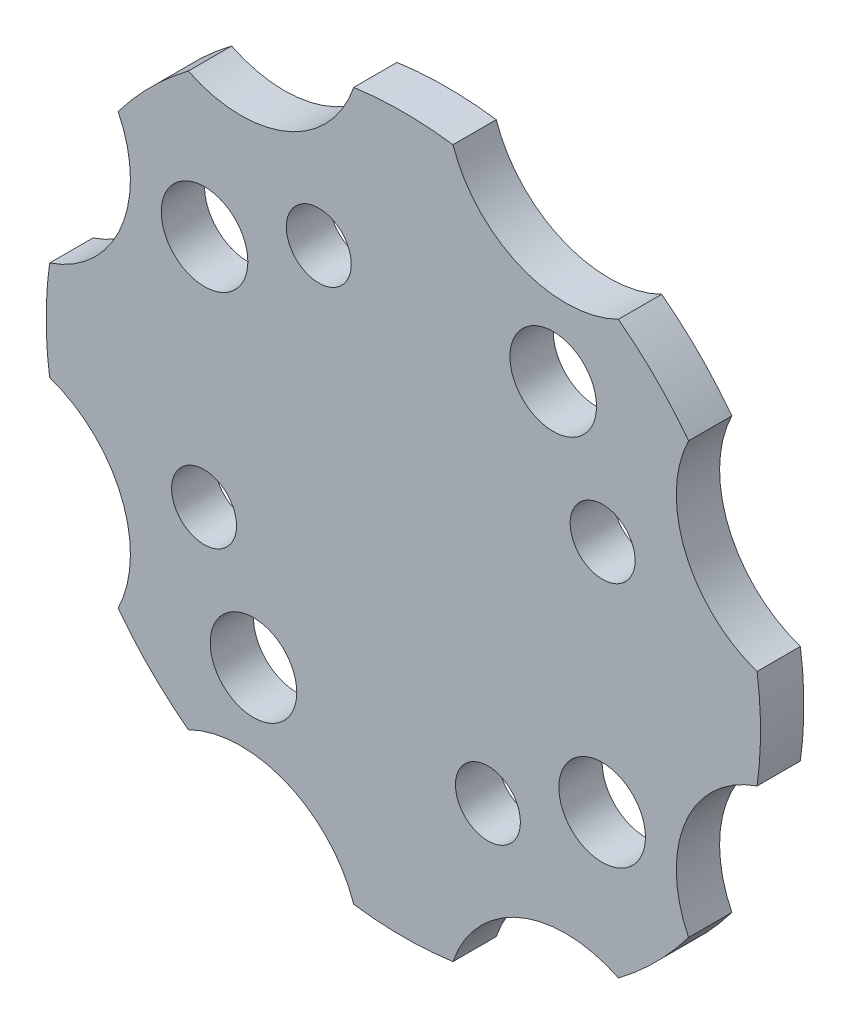
SolidWorks part; units mm, degrees
ref_plane "Front Plane" through (0, 0, 0) normal (0, 0, 1) x (1, 0, 0)
ref_plane "Top Plane" through (0, 0, 0) normal (0, 1, 0) x (1, 0, 0)
ref_plane "Right Plane" through (0, 0, 0) normal (1, 0, 0) x (0, 0, -1)
sketch "Sketch1" plane through (0, 0, 0) normal (0, 0, 1) x (1, 0, 0)
  line L0 (0, 40.4) -> (0, 0)
  line L1 (0, 0) -> (-28.5671, 28.5671)
  line L2 (-27.1179, 29.9463) -> (-11.3901, 14.2185)
  line L3 (-2, 40.3505) -> (-2, 18.108)
  line L4 (2, 40.3505) -> (2, 18.108)
  line L5 (27.1179, 29.9463) -> (11.3901, 14.2185)
  line L6 (29.9463, 27.1179) -> (14.2185, 11.3901)
  line L7 (40.3505, 2) -> (18.108, 2)
  line L8 (40.3505, -2) -> (18.108, -2)
  line L9 (29.9463, -27.1179) -> (14.2185, -11.3901)
  line L10 (27.1179, -29.9463) -> (11.3901, -14.2185)
  line L11 (2, -40.3505) -> (2, -18.108)
  line L12 (-2, -40.3505) -> (-2, -18.108)
  line L13 (-27.1179, -29.9463) -> (-11.3901, -14.2185)
  line L14 (-29.9463, -27.1179) -> (-14.2185, -11.3901)
  line L15 (-40.3505, -2) -> (-18.108, -2)
  line L16 (-40.3505, 2) -> (-18.108, 2)
  line L17 (-29.9463, 27.1179) -> (-14.2185, 11.3901)
  circle A0 centre (0, 0) radius 40.4
  circle A1 centre (0, 0) radius 16.5
  circle A2 centre (0, 0) radius 19.6 construction
  arc A3 (-11.3901, 14.2185) -> (-2, 18.108) centre (-7.5006, 18.108) ccw
  arc A4 (2, 18.108) -> (11.3901, 14.2185) centre (7.5006, 18.108) ccw
  arc A5 (14.2185, 11.3901) -> (18.108, 2) centre (18.108, 7.5006) ccw
  arc A6 (18.108, -2) -> (14.2185, -11.3901) centre (18.108, -7.5006) ccw
  arc A7 (11.3901, -14.2185) -> (2, -18.108) centre (7.5006, -18.108) ccw
  arc A8 (-2, -18.108) -> (-11.3901, -14.2185) centre (-7.5006, -18.108) ccw
  arc A9 (-14.2185, -11.3901) -> (-18.108, -2) centre (-18.108, -7.5006) ccw
  arc A10 (-18.108, 2) -> (-14.2185, 11.3901) centre (-18.108, 7.5006) ccw
  point P49 (0, 0)
  dimension "D1" = 80.8
  dimension "D2" = 33
  dimension "D6" = 39.2
  dimension "D3" = 45
  dimension "D4" = 2
  dimension "D5" = 2
  dimension "D7" = 8
extrude "Boss-Extrude1" add sketch "Sketch1" along normal blind 2 contours A10 A1 A9 A8 A7 A6 A5 A4 L0 L1 | A3 A1 L1 L0 region at (0.5484, -1.3239, 0) region at (-3.8387, 9.2675, 0)
sketch "Sketch2" plane through (0, 0, 2) normal (0, 0, 1) x (1, 0, 0)
  line L0 (0, 0) -> (6.9222, 9.1833) construction
  line L1 (0, 0) -> (9.2056, 3.9059) construction
  circle A0 centre (0, 0) radius 10 construction
  circle A1 centre (0, 0) radius 11.5 construction
  circle A2 centre (9.2056, 3.9059) radius 1.5
  circle A3 centre (6.9222, 9.1833) radius 2
  circle A4 centre (9.1833, -6.9222) radius 2
  circle A5 centre (3.9059, -9.2056) radius 1.5
  circle A6 centre (-6.9222, -9.1833) radius 2
  circle A7 centre (-9.2056, -3.9059) radius 1.5
  circle A8 centre (-9.1833, 6.9222) radius 2
  circle A9 centre (-3.9059, 9.2056) radius 1.5
  point P23 (0, 0)
  dimension "D1" = 23
  dimension "D2" = 20
  dimension "D3" = 4
  dimension "D4" = 3
  dimension "D5" = 30
  dimension "D6" = 4
extrude "Cut-Extrude1" cut sketch "Sketch2" against normal through all
ref_axis "Axis1" through (0, 0, 2) along (0, 0, -1)
